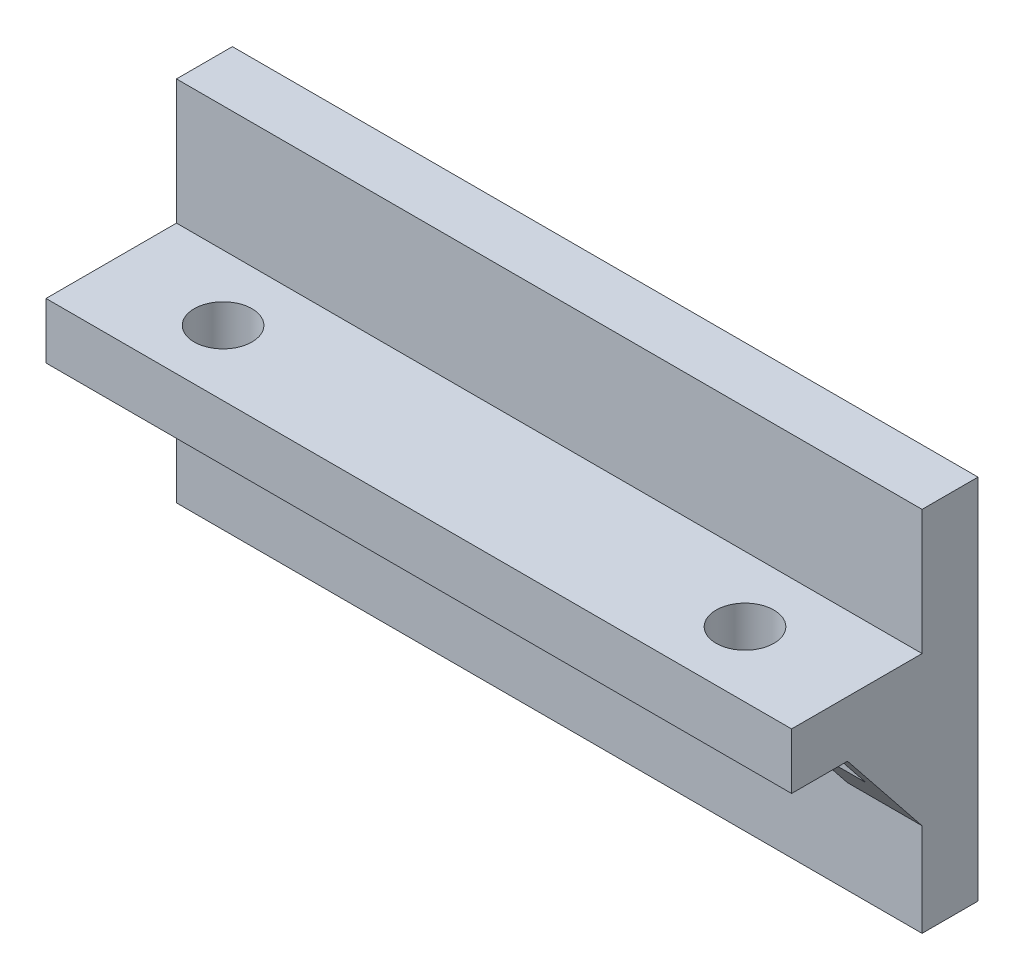
SolidWorks part; units mm, degrees
ref_plane "前视基准面" through (0, 0, 0) normal (0, 0, 1) x (1, 0, 0)
ref_plane "上视基准面" through (0, 0, 0) normal (0, 1, 0) x (1, 0, 0)
ref_plane "右视基准面" through (0, 0, 0) normal (1, 0, 0) x (0, 0, -1)
sketch "草图1" plane through (0, 0, 0) normal (0, 0, 1) x (1, 0, 0)
  line L0 (0, 5) -> (40, 5)
  line L1 (0, 0) -> (40, 0)
  line L2 (0, 0) -> (0, 10)
  line L3 (0, 10) -> (40, 10)
  line L4 (40, 0) -> (40, 10)
  line L5 (40, 5) -> (20, 5)
  line L6 (20, 5) -> (0, 5)
  line L8 (0, 10) -> (40, 10)
  line L9 (0, 10) -> (0, 13)
  line L10 (0, 13) -> (40, 13)
  line L11 (40, 10) -> (40, 13)
  line L12 (0, 13) -> (40, 13)
  line L13 (0, 13) -> (0, 19.7)
  line L14 (0, 19.7) -> (40, 19.7)
  line L15 (40, 13) -> (40, 19.7)
  circle A0 centre (30, 5) radius 1.55
  circle A1 centre (10, 5) radius 1.55
extrude "凸台-拉伸1" add sketch "草图1" along normal blind 3 contours L10 L15 L14 L13 region at (20, 16.35, 0)
extrude "凸台-拉伸2" add sketch "草图1<3>" along normal blind 3 separate body contours A1 L0 L2 L1 L4 A0 | A1 L0 A0 L4 L3 L2 region at (20, 7.5722, 0) region at (20, 2.4278, 0)
sketch "草图1<3>" plane through (0, 0, 0) normal (0, 0, 1) x (1, 0, 0) same geometry as "草图1"
extrude "凸台-拉伸3" add sketch "草图1<5>" along normal blind 10 contours L3 L11 L10 L9 region at (20, 11.5, 0)
sketch "草图1<5>" plane through (0, 0, 0) normal (0, 0, 1) x (1, 0, 0) same geometry as "草图1"
sketch "草图2" plane through (0, 13, 0) normal (0, 1, 0) x (1, 0, 0)
  line L0 (0, -10) -> (0, -6.5)
  line L2 (0, -10) -> (0, -3) construction
  line L3 (0, -6.5) -> (40, -6.5)
  line L4 (40, -10) -> (40, -3) construction
  line L5 (40, -6.5) -> (34, -6.5)
  line L6 (34, -6.5) -> (6, -6.5)
  line L7 (6, -6.5) -> (0, -6.5)
  circle A0 centre (6, -6.5) radius 1.55
  circle A1 centre (34, -6.5) radius 1.55
extrude "切除-拉伸1" cut sketch "草图2" against normal blind 3 contours L3 A0 L7 | L7 A0 L3 | L3 A1 | L3 A1 region at (6, 13, 5.8422) region at (6, 13, 7.1578) region at (34, 13, 5.8422) region at (34, 13, 7.1578)
sketch "草图3" plane through (0, 10, 0) normal (0, -1, 0) x (1, 0, 0)
  line L0 (0, 3) -> (0, 5)
  line L1 (0, 10) -> (0, 3) construction
  line L2 (1, 5) -> (40, 5)
  line L3 (40, 10) -> (40, 3) construction
  line L4 (40, 5) -> (40, 3)
  line L5 (0, 3) -> (40, 3) construction
  line L6 (40, 3) -> (0, 3)
  line L7 (0, 5) -> (0, 3)
  line L8 (1, 5) -> (2, 5)
  line L9 (39, 5) -> (39, 7)
  line L10 (1, 3) -> (0, 3)
  line L11 (40, 5) -> (40, 3)
  line L12 (40, 3) -> (39, 3)
  line L13 (39, 3) -> (39, 5)
  line L14 (39, 7) -> (40, 7)
  line L15 (4.519, 3) -> (1, 3)
  line L16 (1, 5) -> (1, 7)
  line L17 (1, 7) -> (0, 7)
  line L18 (0, 7) -> (0, 5)
  line L19 (1, 5) -> (4, 5)
  line L20 (4, 5) -> (4, 3)
  line L21 (40, 7) -> (39, 7)
  line L22 (39, 5) -> (36, 5)
  line L23 (36, 5) -> (36, 3)
  line L24 (20.5, 5) -> (23.5, 5)
  line L25 (23.5, 5) -> (20.5, 5)
  line L26 (20.5, 5) -> (17.5, 5)
  line L27 (17.5, 5) -> (17.5, 3)
  line L28 (17.5, 3) -> (23.5, 3)
  line L29 (23.5, 3) -> (23.5, 5)
  line M5 (0, 10) -> (0, 3)
  line M6 (0, 3) -> (40, 3)
  line M7 (40, 3) -> (40, 10)
extrude "凸台-拉伸4" add sketch "草图3" along normal blind 5 contours L6 L29 L2 L27 | L20 L2 L16 L17 L6 M5 M6 | L2 L23 L6 L13 | L13 L2 M6 M7 | L14 L9 L2 M7 region at (1.7, 10, 4.4) region at (20.5, 10, 4) region at (37.5, 10, 4) region at (39.5, 10, 4) region at (39.5, 10, 6)
sketch "草图4" plane through (0, 0, 0) normal (-1, 0, 0) x (0, 0, 1)
  line L0 (7, 10) -> (3, 5)
  line L1 (3, 5) -> (7, 5)
  line L2 (7, 5) -> (7, 10)
extrude "切除-拉伸2" cut sketch "草图4" against normal blind 44
